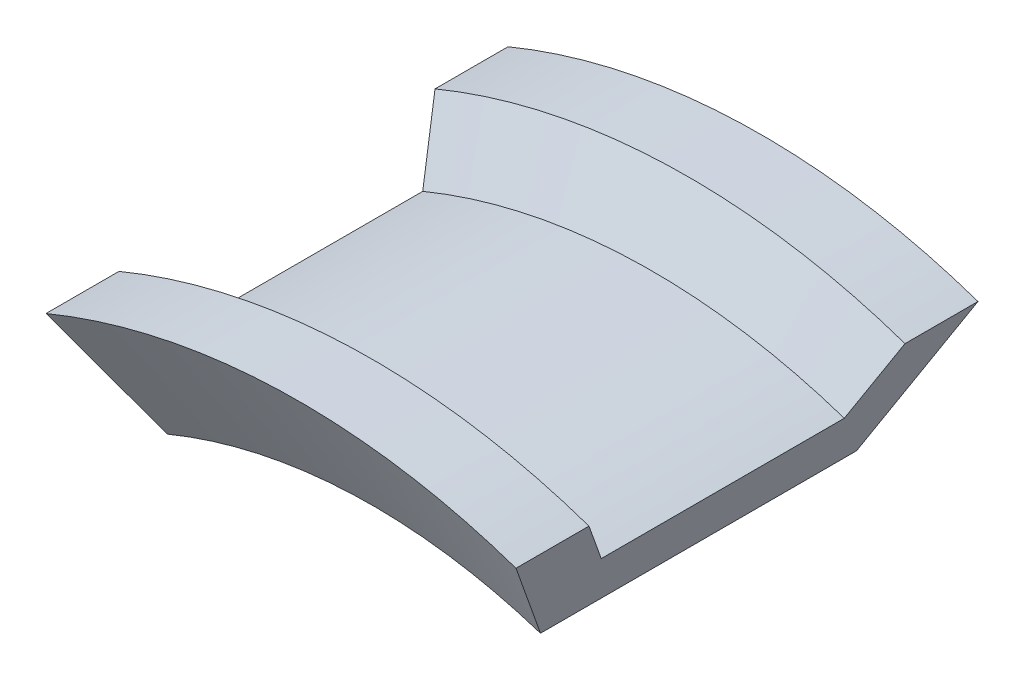
SolidWorks part; units mm, degrees
ref_plane "Front Plane" through (0, 0, 0) normal (0, 0, 1) x (1, 0, 0)
ref_plane "Top Plane" through (0, 0, 0) normal (0, 1, 0) x (1, 0, 0)
ref_plane "Right Plane" through (0, 0, 0) normal (1, 0, 0) x (0, 0, -1)
sketch "Sketch1" plane through (0, 0, 0) normal (0, 0, 1) x (1, 0, 0)
  line L0 (0, 0) -> (0, -93) construction
  line L1 (0, -93) -> (-38.5219, 0)
  line L2 (0, 0) -> (-88.4474, 0) construction
  dimension "D1" = 22.5
  dimension "D2" = 93
ref_plane "Plane1" through (-32.8805, -13.6195, 0) normal (0.9239, 0.3827, 0) x (-0.3827, 0.9239, 0)
ref_plane "Plane4" through (0, 0, 3.2) normal (0, 0, 1) x (1, 0, 0)
sketch "Sketch2" plane through (-32.8805, -13.6195, 0) normal (0.9239, 0.3827, 0) x (-0.3827, 0.9239, 0)
  line L0 (0, 19.2265) -> (0, -19.2265)
  line L1 (0, -19.2265) -> (10, -25)
  line L2 (10, -25) -> (10, -36.547)
  line L3 (10, -36.547) -> (-10, -25)
  line L4 (-10, -25) -> (-10, 25)
  line L5 (0, 0) -> (-30.6463, 0) construction
  line L6 (10, 36.547) -> (-10, 25)
  line L7 (10, 25) -> (10, 36.547)
  line L8 (0, 19.2265) -> (10, 25)
  point P3 (10, -30.7735)
  point P10 (-10, 0)
  dimension "D1" = 25
  dimension "D2" = 10
  dimension "D3" = 10
  dimension "D4" = 30
  dimension "D5" = 10
sketch "Sketch3" plane through (0, 0, 0) normal (0, 0, 1) x (1, 0, 0)
  line L0 (-32.8805, -13.6195) -> (115.9824, -13.6195) construction
  line L2 (39.8294, -13.6195) -> (-32.8805, -189.1566) construction
  line L3 (-32.8805, -13.6195) -> (39.8294, -189.1566) construction
  line L6 (0, -93) -> (-38.5219, 0) construction
  arc A0 (-32.8805, -13.6195) -> (39.8294, -13.6195) centre (3.4745, -101.3881) cw
  dimension "D1" = 95
sweep "Sweep1" add profiles "Sketch2" path "Sketch3"
sketch "Sketch4" plane through (0, 0, 3.2) normal (1, 0, 0) x (0, 0, -1)
  line L0 (3.2, 0) -> (3.2, -54) construction
  line L1 (9.4785, -28.6823) -> (12.7727, -16.3881)
  line L2 (-3.0785, -28.6823) -> (-6.3727, -16.3881)
  line L11 (28.2, -16.3881) -> (-21.8, -16.3881) construction
  line L12 (12.7727, -16.3881) -> (-6.3727, -16.3881)
  arc A2 (-3.0785, -28.6823) -> (9.4785, -28.6823) centre (3.2, -27) ccw
  circle A3 centre (3.2, -27) radius 3
  dimension "D1" = 6.5
  dimension "D2" = 6
  dimension "D3" = 27
  dimension "D4" = 30
ref_axis "Axis1" through (0, -98.5061, 0) along (0, 1, 0)
ref_axis "Axis2" through (0, 0, 40.2017) along (0, 0, -1)
ref_axis "Axis3" through (-94.9757, 0, 0) along (1, 0, 0)
ref_plane "Plane2" through (0, 0, 0) normal (0.9239, -0.3827, 0) x (0, 0, -1)
ref_plane "Plane3" through (32.8805, -13.6195, 0) normal (0.9239, -0.3827, 0) x (0, 0, -1)
sketch "Sketch5" plane through (32.8805, -13.6195, 0) normal (0.9239, -0.3827, 0) x (0, 0, -1)
  line L1 (-45, 35) -> (45, 35)
  line L2 (-45, 35) -> (-45, -35)
  line L3 (-45, -35) -> (45, -35)
  line L4 (45, 35) -> (45, -35)
  line L5 (-45, 35) -> (45, -35) construction
  line L6 (-45, -35) -> (45, 35) construction
  point P0 (0, 0)
  dimension "D1" = 90
  dimension "D2" = 70
extrude "Cut-Extrude1" cut sketch "Sketch5" along normal through all contours L1 L4 L3 L2
extrude "Boss-Extrude3" add sketch "Sketch4" along normal blind 3.2 separate body
move or copy body "Body-Move/Copy1" bodies to move or copy 105 copy yes number of copies 1 translate (6.4, 0, 0)
move or copy body "Body-Move/Copy2" bodies to move or copy 105 copy yes number of copies 1 translate (-6.4, 0, 0)
sketch "Sketch6" plane through (9.6, 0, 0) normal (1, 0, 0) x (0, 0, -1)
  circle A0 centre (0, -27) radius 5.25
  dimension "D1" = 10.5
extrude "Cut-Extrude2" cut sketch "Sketch6" against normal blind 1.75
